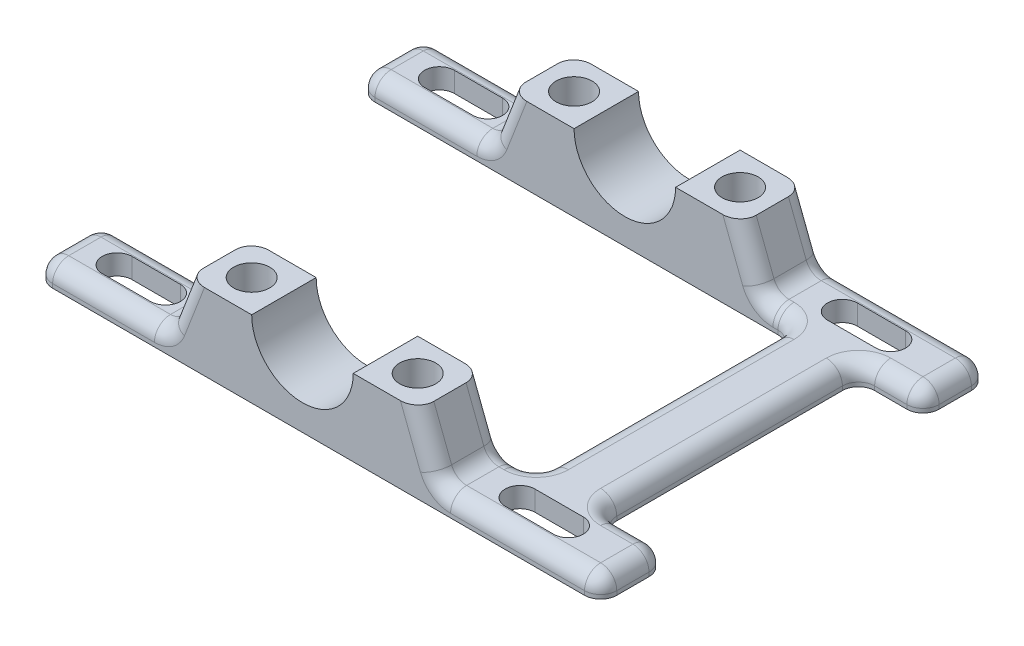
SolidWorks part; units mm, degrees
ref_plane "Front Plane" through (0, 0, 0) normal (0, 0, 1) x (1, 0, 0)
ref_plane "Top Plane" through (0, 0, 0) normal (0, 1, 0) x (1, 0, 0)
ref_plane "Right Plane" through (0, 0, 0) normal (1, 0, 0) x (0, 0, -1)
sketch "Sketch1" plane through (0, 0, 0) normal (0, 1, 0) x (1, 0, 0)
  line L1 (-88.9, 0) -> (0, 0)
  line L2 (-88.9, 0) -> (-88.9, -30.48)
  line L3 (-88.9, -30.48) -> (0, -30.48)
  line L4 (0, 0) -> (0, -30.48)
  dimension "D1" = 30.48
  dimension "D2" = 88.9
extrude "Boss-Extrude1" add sketch "Sketch1" along normal blind 3.175
sketch "Sketch2" plane through (0, 0, 30.48) normal (0, 0, 1) x (1, 0, 0)
  line L0 (-68.58, 3.175) -> (-65.151, 12.065)
  line L1 (-88.9, 3.175) -> (0, 3.175) construction
  line L2 (-65.151, 12.065) -> (-54.991, 12.065)
  line L3 (-28.829, 12.065) -> (-25.4, 3.175)
  line L4 (-25.4, 3.175) -> (-68.58, 3.175)
  line L5 (-38.989, 12.065) -> (-28.829, 12.065)
  line L6 (-46.99, 12.065) -> (-46.99, 3.175) construction
  line L7 (-54.991, 12.065) -> (-38.989, 12.065) construction
  arc A0 (-54.991, 12.065) -> (-38.989, 12.065) centre (-46.99, 12.065) ccw
  point P1 (-46.99, 12.065)
  dimension "D1" = 16.002
  dimension "D2" = 10.16
  dimension "D3" = 43.18
  dimension "D4" = 25.4
  dimension "D5" = 8.89
extrude "Boss-Extrude2" add sketch "Sketch2" against normal blind 10.16
sketch "Sketch3" plane through (0, 0, 0) normal (0, 1, 0) x (1, 0, 0)
  line L0 (-88.9, 0) -> (-88.9, -30.48) construction
  line L1 (-88.9, -20.32) -> (-20.32, -20.32)
  line L2 (-88.9, -20.32) -> (-88.9, 0)
  line L3 (-88.9, 0) -> (-20.32, 0)
  line L4 (-20.32, -20.32) -> (-20.32, 0)
  line L8 (0, 0) -> (-88.9, 0) construction
  line L9 (-25.4, -30.48) -> (0, -30.48) construction
  line L10 (-10.16, 0) -> (-10.16, -20.32)
  line L11 (-10.16, -20.32) -> (0, -20.32)
  line L12 (0, -30.48) -> (0, 0) construction
  line L13 (0, -20.32) -> (0, 0)
  line L14 (0, 0) -> (-10.16, 0)
  dimension "D1" = 10.16
  dimension "D2" = 10.16
  dimension "D3" = 10.16
extrude "Cut-Extrude1" cut sketch "Sketch3" along normal through all
sketch "Sketch5" plane through (0, 12.065, 0) normal (0, 1, 0) x (1, 0, 0)
  line L1 (-38.989, -30.48) -> (-28.829, -30.48) construction
  line L2 (-38.989, -30.48) -> (-38.989, -20.32) construction
  line L3 (-38.989, -20.32) -> (-28.829, -20.32) construction
  line L4 (-28.829, -30.48) -> (-28.829, -20.32) construction
  line L5 (-38.989, -30.48) -> (-28.829, -20.32) construction
  line L6 (-38.989, -20.32) -> (-28.829, -30.48) construction
  line L7 (-65.151, -30.48) -> (-54.991, -30.48) construction
  line L8 (-65.151, -30.48) -> (-65.151, -20.32) construction
  line L9 (-65.151, -20.32) -> (-54.991, -20.32) construction
  line L10 (-54.991, -30.48) -> (-54.991, -20.32) construction
  line L11 (-65.151, -30.48) -> (-54.991, -20.32) construction
  line L12 (-65.151, -20.32) -> (-54.991, -30.48) construction
  circle A0 centre (-33.909, -25.4) radius 2.8448
  circle A1 centre (-60.071, -25.4) radius 2.8448
  point P0 (-33.909, -25.4)
  point P5 (-60.071, -25.4)
  dimension "D1" = 5.6896
extrude "Cut-Extrude2" cut sketch "Sketch5" against normal blind 12.7
sketch "Sketch6" plane through (0, 3.175, 0) normal (0, 1, 0) x (1, 0, 0)
  line L0 (-88.9, -25.4) -> (0, -25.4) construction
  line L1 (-88.9, -20.32) -> (-88.9, -30.48) construction
  line L2 (0, -30.48) -> (0, -20.32) construction
  line L3 (-81.28, -25.4) -> (-73.66, -25.4) construction
  line L4 (-81.28, -23.0505) -> (-73.66, -23.0505)
  line L5 (-81.28, -27.7495) -> (-73.66, -27.7495)
  line L6 (-17.78, -25.4) -> (-10.16, -25.4) construction
  line L7 (-17.78, -23.0505) -> (-10.16, -23.0505)
  line L8 (-17.78, -27.7495) -> (-10.16, -27.7495)
  arc A0 (-81.28, -23.0505) -> (-81.28, -27.7495) centre (-81.28, -25.4) ccw
  arc A1 (-73.66, -27.7495) -> (-73.66, -23.0505) centre (-73.66, -25.4) ccw
  arc A2 (-17.78, -23.0505) -> (-17.78, -27.7495) centre (-17.78, -25.4) ccw
  arc A3 (-10.16, -27.7495) -> (-10.16, -23.0505) centre (-10.16, -25.4) ccw
  point P8 (-77.47, -25.4)
  point P13 (-13.97, -25.4)
  dimension "D1" = 4.699
  dimension "D2" = 7.62
  dimension "D3" = 63.5
  dimension "D4" = 10.16
extrude "Cut-Extrude3" cut sketch "Sketch6" against normal through all
mirror "Mirror4" about plane through (0, 0, 0) normal (0, 0, 1) of "Cut-Extrude3", "Cut-Extrude2", "Cut-Extrude1", "Boss-Extrude2", "Boss-Extrude1"
fillet "Fillet1" radius 2.54 40 edges at (-78.74, 3.175, -30.48) (-66.8655, 7.62, -20.32) (-78.74, 3.175, 20.32) (-12.7, 3.175, -30.48) (-27.1145, 7.62, -20.32) (-22.86, 3.175, 20.32) (-20.32, 1.5875, -20.32) (-20.32, 1.5875, 20.32) (0, 1.5875, -30.48) (0, 1.5875, 30.48) (-88.9, 1.5875, 20.32) (-88.9, 1.5875, 30.48) (-88.9, 1.5875, -30.48) (-88.9, 1.5875, -20.32) (-88.9, 3.175, -25.4) (-66.8655, 7.62, -30.48) (-78.74, 3.175, -20.32) (-88.9, 3.175, 25.4) (-66.8655, 7.62, 20.32) (0, 3.175, 25.4) (-27.1145, 7.62, -30.48) (-22.86, 3.175, -20.32) (-27.1145, 7.62, 20.32) (-25.4, 3.175, -25.4) (-68.58, 3.175, -25.4) (0, 1.5875, 20.32) (-10.16, 1.5875, 20.32) (-10.16, 1.5875, -20.32) (0, 1.5875, -20.32) (0, 3.175, -25.4) (-5.08, 3.175, -20.32) (-5.08, 3.175, 20.32)
